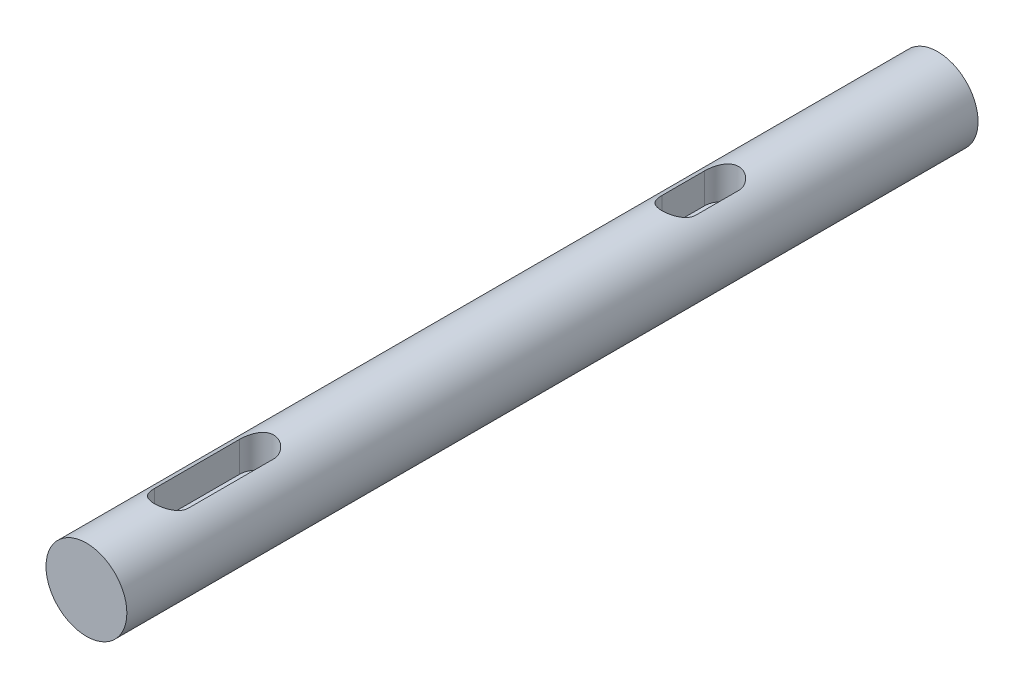
SolidWorks part; units mm, degrees
ref_plane "Front Plane" through (0, 0, 0) normal (0, 0, 1) x (1, 0, 0)
ref_plane "Top Plane" through (0, 0, 0) normal (0, 1, 0) x (1, 0, 0)
ref_plane "Right Plane" through (0, 0, 0) normal (1, 0, 0) x (0, 0, -1)
sketch "Sketch1" plane through (0, 0, 0) normal (0, 0, 1) x (1, 0, 0)
  circle A0 centre (0, 0) radius 4.75
  dimension "D1" = 9.5
extrude "Boss-Extrude1" add sketch "Sketch1" along normal blind 0.0001
sketch "Sketch4" plane through (0, 0, 0) normal (0, 0, -1) x (-1, 0, 0)
  circle A0 centre (0, 0) radius 4.75
  dimension "D1" = 9.5
extrude "Boss-Extrude2" add sketch "Sketch4" along normal blind 105
ref_axis "Axis1" through (0, 0, -132.4687) along (0, 0, 1)
ref_plane "Plane1" through (0, 4.75, 0) normal (0, 1, 0) x (1, 0, 0)
sketch "Sketch5" plane through (0, 4.75, 0) normal (0, 1, 0) x (1, 0, 0)
  line L0 (0, -4.3175) -> (0, 99.6122) construction
  line L1 (0, 10) -> (0, 20) construction
  line L2 (-2, 10) -> (-2, 20)
  line L3 (2, 10) -> (2, 20)
  line L11 (0, 69.62) -> (0, 74.62) construction
  line L12 (-2, 69.62) -> (-2, 74.62)
  line L13 (2, 69.62) -> (2, 74.62)
  arc A0 (-2, 10) -> (2, 10) centre (0, 10) ccw
  arc A1 (2, 20) -> (-2, 20) centre (0, 20) ccw
  arc A6 (-2, 69.62) -> (2, 69.62) centre (0, 69.62) ccw
  arc A7 (2, 74.62) -> (-2, 74.62) centre (0, 74.62) ccw
  point P5 (0, 15)
  point P28 (0, 72.12)
  dimension "D1" = 10
  dimension "D2" = 4
  dimension "D4" = 49.62
  dimension "D11" = 2.5
  dimension "D12" = 4
extrude "Cut-Extrude3" cut sketch "Sketch5" against normal blind 4
sketch "Sketch6" plane through (0, 0, -105) normal (0, 0, -1) x (-1, 0, 0)
  circle A0 centre (0, 0) radius 4.75
extrude "Cut-Extrude4" cut sketch "Sketch6" against normal blind 5
